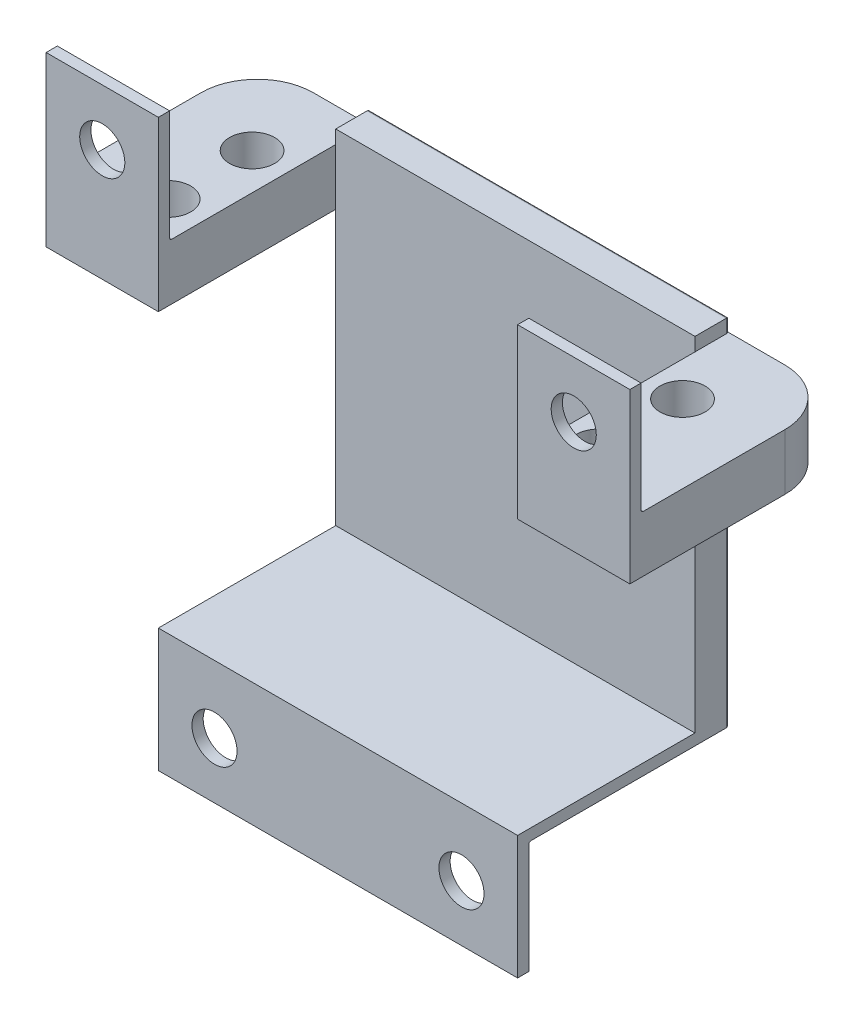
SolidWorks part; units mm, degrees
ref_plane "Front Plane" through (0, 0, 0) normal (0, 0, 1) x (1, 0, 0)
ref_plane "Top Plane" through (0, 0, 0) normal (0, 1, 0) x (1, 0, 0)
ref_plane "Right Plane" through (0, 0, 0) normal (1, 0, 0) x (0, 0, -1)
sketch "Sketch1" plane through (0, 0, 0) normal (0, 1, 0) x (1, 0, 0)
  line L1 (0, 0) -> (12.7, 0)
  line L2 (0, 0) -> (0, 18.796)
  line L3 (0, 18.796) -> (12.7, 18.796)
  line L4 (12.7, 0) -> (12.7, 18.796)
  dimension "D1" = 12.7
  dimension "D2" = 18.796
extrude "Boss-Extrude1" add sketch "Sketch1" along normal blind 6.35
sketch "Sketch2" plane through (0, 6.35, 0) normal (0, 1, 0) x (1, 0, 0)
  line L2 (0, 0) -> (12.7, 0) construction
  line L3 (6.35, 0) -> (8.89, 0) construction
  line L6 (12.7, 18.796) -> (0, 18.796) construction
  line L8 (0, 18.796) -> (0, 0) construction
  circle A9 centre (8.5526, 14.75) radius 2.5527
  circle A10 centre (8.5526, 5.25) radius 2.5527
  dimension "D1" = 5.1054
  dimension "D2" = 5.1054
  dimension "D4" = 4.046
  dimension "D3" = 9.5
  dimension "D5" = 8.5526
  dimension "D6" = 8.5526
extrude "Cut-Extrude1" cut sketch "Sketch2" against normal up to surface (6.35 mm away) contours A9 | A10 up to face at (6.35, 0, -9.398)
sketch "Sketch3" plane through (0, 0, -18.796) normal (0, 0, -1) x (-1, 0, 0)
  line L6 (0, 0) -> (-66.04, 0)
  line L7 (0, 0) -> (0, 6.35)
  line L8 (0, 6.35) -> (-66.04, 6.35)
  line L9 (-66.04, 0) -> (-66.04, 6.35)
  dimension "D1" = 6.35
  dimension "D2" = 66.04
extrude "Boss-Extrude2" add sketch "Sketch3" along normal blind 5.08
sketch "Sketch4" plane through (0, 0, -23.876) normal (0, 0, -1) x (-1, 0, 0)
  line L0 (0, 6.35) -> (-66.04, 6.35) construction
  line L1 (-53.34, 6.35) -> (-12.7, 6.35)
  line L2 (-53.34, 6.35) -> (-53.34, 7.874)
  line L3 (-53.34, 7.874) -> (-12.7, 7.874)
  line L4 (-12.7, 6.35) -> (-12.7, 7.874)
  dimension "D1" = 1.524
  dimension "D2" = 40.64
  dimension "D3" = 12.7
extrude "Boss-Extrude5" add sketch "Sketch4" against normal blind 3.81
sketch "Sketch9" plane through (0, 0, -23.876) normal (0, 0, -1) x (-1, 0, 0)
  line L9 (-12.7, 7.874) -> (-12.7, 0) construction
  line L11 (-12.7, 0) -> (-53.34, 0)
  line L12 (-12.7, 0) -> (-12.7, -30.988)
  line L13 (-12.7, -30.988) -> (-53.34, -30.988)
  line L14 (-53.34, 0) -> (-53.34, -30.988)
  dimension "D1" = 40.64
  dimension "D2" = 30.988
extrude "Boss-Extrude6" add sketch "Sketch9" against normal blind 3.81
sketch "Sketch10" plane through (0, 0, -18.796) normal (0, 0, 1) x (1, 0, 0)
  line L7 (12.7, 6.35) -> (66.04, 6.35)
  line L8 (12.7, 6.35) -> (12.7, 0)
  line L9 (12.7, 0) -> (66.04, 0)
  line L10 (66.04, 6.35) -> (66.04, 0)
extrude "Cut-Extrude3" cut sketch "Sketch10" against normal up to surface (1.27 mm away) up to face at (33.02, 7.112, -20.066)
sketch "Sketch11" plane through (0, 0, 0) normal (0, 0, 1) x (1, 0, 0)
  line L17 (12.7, 0) -> (0, 0)
  line L18 (12.7, 0) -> (12.7, 19.05)
  line L19 (12.7, 19.05) -> (0, 19.05)
  line L20 (0, 0) -> (0, 19.05)
  dimension "D1" = 19.05
  dimension "D2" = 12.7
extrude "Boss-Extrude7" add sketch "Sketch11" against normal blind 1.27
sketch "Sketch16" plane through (0, 0, -1.27) normal (0, 0, -1) x (-1, 0, 0)
  line L0 (-6.35, 6.35) -> (-6.35, 19.05) construction
  line L3 (-12.7, 6.35) -> (0, 6.35) construction
  line L4 (-12.7, 19.05) -> (0, 19.05) construction
  circle A1 centre (-6.35, 12.7) radius 2.5527
  dimension "D1" = 5.1054
extrude "Cut-Extrude5" cut sketch "Sketch16" against normal up to surface (1.27 mm away) up to face at (6.35, 9.525, 0)
sketch "Sketch17" plane through (0, 0, -23.876) normal (0, 0, -1) x (-1, 0, 0)
  line L1 (-53.34, 6.35) -> (-66.04, 6.35)
  line L2 (-53.34, 6.35) -> (-53.34, 0)
  line L3 (-53.34, 0) -> (-66.04, 0)
  line L4 (-66.04, 6.35) -> (-66.04, 0)
extrude "Boss-Extrude8" add sketch "Sketch17" against normal blind 23.876
sketch "Sketch20" plane through (0, 6.35, 0) normal (0, 1, 0) x (1, 0, 0)
  line L0 (53.34, 23.876) -> (66.04, 23.876) construction
  line L1 (53.34, 0) -> (66.04, 0) construction
  line L2 (53.34, 0) -> (53.34, 20.066) construction
  circle A4 centre (57.2474, 14.75) radius 2.5527
  circle A5 centre (57.2474, 5.25) radius 2.5527
  dimension "D1" = 5.1054
  dimension "D2" = 5.1054
  dimension "D3" = 9.5
  dimension "D4" = 9.126
  dimension "D5" = 5.25
  dimension "D6" = 3.9074
extrude "Cut-Extrude6" cut sketch "Sketch20" against normal up to surface (6.35 mm away) contours A4 | A5 up to face at (58.42, 0, -13.5636)
sketch "Sketch21" plane through (0, 0, 0) normal (0, 0, 1) x (1, 0, 0)
  line L5 (66.04, 0) -> (53.34, 0)
  line L6 (66.04, 0) -> (66.04, 19.05)
  line L7 (66.04, 19.05) -> (53.34, 19.05)
  line L8 (53.34, 0) -> (53.34, 19.05)
  dimension "D1" = 12.7
  dimension "D2" = 19.05
extrude "Boss-Extrude9" add sketch "Sketch21" against normal blind 1.27
sketch "Sketch22" plane through (0, 0, -1.27) normal (0, 0, -1) x (-1, 0, 0)
  line L0 (-59.69, 19.05) -> (-59.69, 6.35) construction
  line L3 (-66.04, 19.05) -> (-53.34, 19.05) construction
  line L4 (-66.04, 6.35) -> (-53.34, 6.35) construction
  circle A1 centre (-59.69, 12.7) radius 2.5527
  dimension "D1" = 5.1054
extrude "Cut-Extrude7" cut sketch "Sketch22" against normal up to surface (1.27 mm away) contours A1 up to face at (59.69, 9.525, 0)
sketch "Sketch23" plane through (0, -30.988, 0) normal (0, -1, 0) x (1, 0, 0)
  line L1 (53.34, -23.876) -> (12.7, -23.876)
  line L2 (53.34, -23.876) -> (53.34, 0)
  line L3 (53.34, 0) -> (12.7, 0)
  line L4 (12.7, -23.876) -> (12.7, 0)
  dimension "D1" = 40.64
  dimension "D2" = 23.876
extrude "Boss-Extrude10" add sketch "Sketch23" along normal blind 1.27
sketch "Sketch24" plane through (0, 0, 0) normal (0, 0, 1) x (1, 0, 0)
  line L1 (12.7, -30.988) -> (53.34, -30.988)
  line L2 (12.7, -30.988) -> (12.7, -44.958)
  line L3 (12.7, -44.958) -> (53.34, -44.958)
  line L4 (53.34, -30.988) -> (53.34, -44.958)
  dimension "D1" = 40.64
  dimension "D2" = 13.97
extrude "Boss-Extrude11" add sketch "Sketch24" against normal blind 1.27
sketch "Sketch25" plane through (0, 0, -1.27) normal (0, 0, -1) x (-1, 0, 0)
  line L0 (-53.34, -44.958) -> (-40.64, -44.958) construction
  line L1 (-12.7, -44.958) -> (-53.34, -44.958) construction
  line L2 (-40.64, -44.958) -> (-40.64, -32.258) construction
  line L3 (-12.7, -32.258) -> (-53.34, -32.258) construction
  line L4 (-40.64, -32.258) -> (-53.34, -44.958) construction
  line L5 (-25.4, -32.258) -> (-25.4, -44.958) construction
  line L6 (-53.34, -32.258) -> (-12.7, -32.258) construction
  line L7 (-25.4, -44.958) -> (-12.7, -44.958) construction
  line L8 (-12.7, -44.958) -> (-25.4, -32.258) construction
  circle A0 centre (-46.99, -38.608) radius 2.5527
  circle A1 centre (-19.05, -38.608) radius 2.5527
  dimension "D2" = 5.1054
  dimension "D4" = 5.1054
  dimension "D1" = 12.7
  dimension "D3" = 12.7
extrude "Cut-Extrude8" cut sketch "Sketch25" against normal up to surface (1.27 mm away) contours A0 | A1 up to face at (33.02, -37.973, 0)
fillet "Fillet4" radius 6.35 2 edges at (0, 3.175, -23.876) (66.04, 3.175, -23.876)
fillet "Fillet5" radius 0.254 9 edges at (33.02, -32.258, -1.27) (59.69, 6.35, -1.27) (6.35, 6.35, -1.27) (12.7, -16.129, -23.876) (33.02, -32.258, -23.876) (53.34, -16.129, -23.876) (33.02, 7.874, -23.876) (53.34, 7.112, -23.876) (12.7, 7.112, -23.876)
